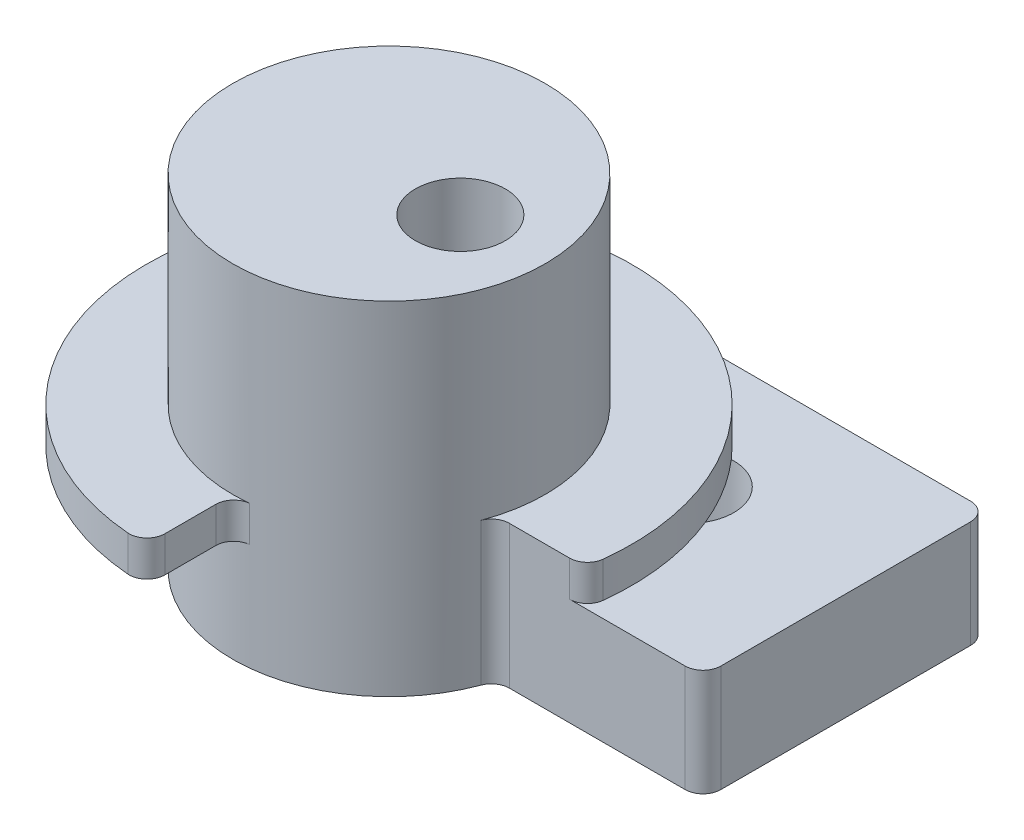
SolidWorks part; units mm, degrees
material "PET"
ref_plane "Front Plane" through (0, 0, 0) normal (1, 0, 0) x (0, 1, 0)
ref_plane "Top Plane" through (0, 0, 0) normal (0, 0, 1) x (0, 1, 0)
ref_plane "Right Plane" through (0, 0, 0) normal (0, 1, 0) x (-1, 0, 0)
sketch "Sketch2" plane through (0, 0, 0) normal (0, 0, 1) x (0, 1, 0)
  line L0 (0, 6.95) -> (0, -6.95) construction
  line L1 (15.24, -6.95) -> (-15.24, -6.95)
  line L2 (15.24, -6.95) -> (15.24, 6.95)
  line L3 (15.24, 6.95) -> (-15.24, 6.95)
  line L4 (-15.24, -6.95) -> (-15.24, 6.95)
  line L5 (15.24, -6.95) -> (-15.24, 6.95) construction
  line L6 (15.24, 6.95) -> (-15.24, -6.95) construction
  line L11 (-10.4775, 10.795) -> (-8.89, 10.795)
  line L12 (-10.4775, 10.795) -> (-10.4775, -10.795)
  line L19 (-10.4775, -10.795) -> (-8.89, -10.795)
  line L20 (-8.89, 10.795) -> (-8.89, -10.795)
  line L21 (10.4775, -10.795) -> (8.89, -10.795)
  line L22 (8.89, 10.795) -> (8.89, -10.795)
  line L23 (10.4775, 10.795) -> (8.89, 10.795)
  line L24 (10.4775, 10.795) -> (10.4775, -10.795)
  line L25 (-15.24, 0) -> (15.24, 0)
  point P0 (0, 0)
  point P6 (0, 0)
  point P11 (0, 0)
  point P16 (-10.4775, 0)
  dimension "D1" = 13.9
  dimension "D2" = 30.48
  dimension "D5" = 1.5875
  dimension "D6" = 21.59
  dimension "D7" = 8.89
revolve "Revolve2" add sketch "Sketch2" angle 360 about L25 region at (-3.475, 12.8588, 0) region at (-3.475, 9.6838, 0) region at (-3.475, 0, 0) region at (-8.8725, 9.6838, 0) region at (-3.475, -9.6838, 0) region at (-3.475, -12.8588, 0) region at (-8.8725, -9.6838, 0)
sketch "Sketch3" plane through (0, 0, 0) normal (0, 1, 0) x (-1, 0, 0)
  circle A0 centre (0, 0) radius 11.3381
extrude "Cut-Extrude1" cut sketch "Sketch3" against normal blind 21.336
sketch "Sketch5" plane through (0, 15.24, 0) normal (0, 1, 0) x (-1, 0, 0)
  line L5 (0, -10.795) -> (-15.875, -10.795)
  line L6 (0, -10.795) -> (0, 1.905)
  line L7 (0, 1.905) -> (-15.875, 1.905)
  line L8 (-15.875, -10.795) -> (-15.875, 1.905)
  circle A0 centre (-3.175, 0) radius 2
  circle A1 centre (0, 0) radius 6.95 construction
  circle A2 centre (0, 0) radius 6.95 construction
  circle A3 centre (-3.175, 0) radius 3.6 construction
  circle A9 centre (0, 0) radius 6.95
  circle A10 centre (-8.255, -5.08) radius 2
  circle A13 centre (0, 0) radius 10.795 construction
  circle A14 centre (-8.255, -5.08) radius 3.6 construction
  circle A15 centre (0, 0) radius 10.541 construction
  point P4 (6.95, 0)
  point P13 (-3.175, 2)
  point P15 (-3.175, 3.6)
  point P20 (-6.255, -5.08)
  point P21 (-4.655, -5.08)
  circle M7 centre (0, 0) radius 6.95
  dimension "D8" = 1.6
  dimension "D3" = 4
  dimension "D7" = 15.875
  dimension "D10" = 21.082
  dimension "D2" = 3.175
  dimension "D4" = 5.08
  dimension "D5" = 1.6
  dimension "D6" = 12.7
  dimension "D9" = 5.08
  dimension "5" = 0
extrude "Cut-Extrude3" cut sketch "Sketch5" against normal blind 27.432 contours A0 | L7 A0 region at (3.175, 15.24, -0.0121) region at (3.175, 15.24, 1.9431)
extrude "Boss-Extrude2" add sketch "Sketch5<3>" against normal up to surface (4.7625 mm away) contours L8 A10 M7 region at (7.9375, 15.24, -10.5917) up to face at (6.95, 10.4775, 0)
sketch "Sketch5<3>" plane through (0, 15.24, 0) normal (0, 1, 0) x (-1, 0, 0) same geometry as "Sketch5"
fillet "Fillet1" radius 0.7937 5 edges at (0, 12.8588, -10.795) (0, 12.8588, -6.95) (15.875, 12.8588, -10.795) (6.6838, 12.8588, 1.905) (15.875, 12.8588, 1.905)
sketch "Sketch6" plane through (0, 10.4775, 0) normal (0, 1, 0) x (-1, 0, 0)
  line L0 (0, 6.95) -> (0, 10.795)
  line L3 (0, -7.703) -> (0, -10.0013)
  line L4 (-10.6256, 1.905) -> (-7.2583, 1.905)
  line L5 (0, -7.703) -> (0, -10.0013)
  line L6 (-10.6256, 1.905) -> (-7.2583, 1.905)
  arc A0 (0.7124, -6.9134) -> (-6.5143, 2.4221) centre (0, 0) ccw construction
  arc A1 (-0.6251, -10.7769) -> (-10.6256, 1.905) centre (0, 0) ccw construction
  arc A7 (0.7124, -6.9134) -> (-6.5143, 2.4221) centre (0, 0) ccw
  arc A8 (0.7124, -6.9134) -> (0, -7.703) centre (0.7938, -7.703) ccw
  arc A9 (-0.6251, -10.7769) -> (0, -10.0013) centre (-0.7937, -10.0013) ccw
  arc A10 (-0.6251, -10.7769) -> (-10.6256, 1.905) centre (0, 0) ccw
  arc A11 (-7.2583, 1.905) -> (-6.5143, 2.4221) centre (-7.2583, 2.6987) ccw
  arc A12 (0.7124, -6.9134) -> (-6.5143, 2.4221) centre (0, 0) ccw
  arc A13 (0.7124, -6.9134) -> (0, -7.703) centre (0.7938, -7.703) ccw
  arc A14 (-0.6251, -10.7769) -> (0, -10.0013) centre (-0.7937, -10.0013) ccw
  arc A15 (-0.6251, -10.7769) -> (-10.6256, 1.905) centre (0, 0) ccw
  arc A16 (-7.2583, 1.905) -> (-6.5143, 2.4221) centre (-7.2583, 2.6987) ccw
  arc M8 (-6.5143, 2.4221) -> (0.7124, -6.9134) centre (0, 0) cw
  arc M12 (-0.6251, -10.7769) -> (-10.6256, 1.905) centre (0, 0) ccw
  line M13 (-10.6256, 1.905) -> (-7.2583, 1.905)
  arc M14 (-7.2583, 1.905) -> (-6.5143, 2.4221) centre (-7.2583, 2.6987) ccw
  dimension "D1" = 0
extrude "Cut-Extrude4" cut sketch "Sketch6" against normal blind 14.224 contours L0 M8 M12 M13 M14 region at (5.2452, 10.4775, 6.5067)
fillet "Fillet2" radius 0.7937 3 edges at (10.6256, 9.6838, 1.905) (0, 9.6838, 6.95) (0, 9.6838, 10.795)
mirror "Mirror1" about plane through (0, 0, 0) normal (0, 1, 0) of bodies 109
delete or keep bodies "Body-Delete/Keep 1" type delete bodies bodies 109
